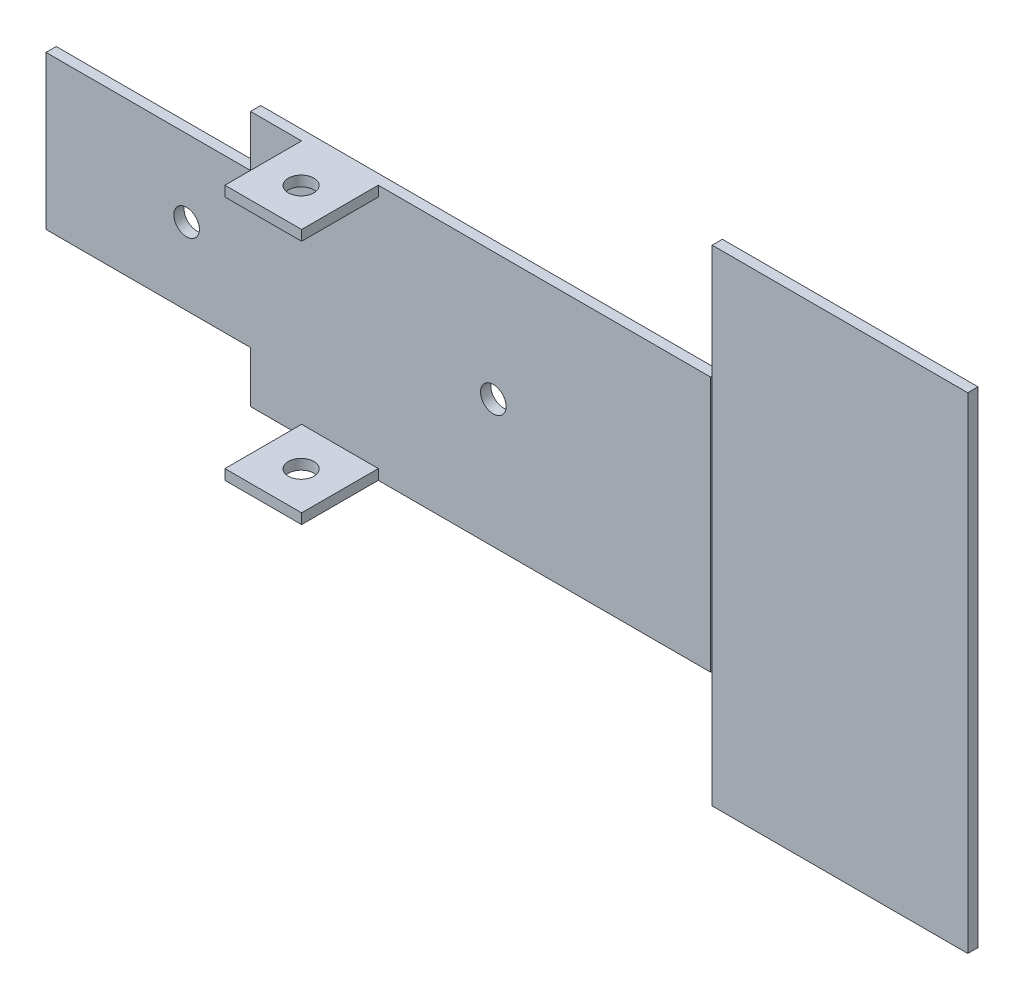
SolidWorks part; units mm, degrees
ref_plane "Front Plane" through (0, 0, 0) normal (0, 0, 1) x (1, 0, 0)
ref_plane "Top Plane" through (0, 0, 0) normal (0, 1, 0) x (1, 0, 0)
ref_plane "Right Plane" through (0, 0, 0) normal (1, 0, 0) x (0, 0, -1)
sketch "Sketch1" plane through (0, 0, 0) normal (0, 0, 1) x (1, 0, 0)
  line L1 (-65, -25) -> (65, -25)
  line L2 (-65, -25) -> (-65, 25)
  line L3 (-65, 25) -> (65, 25)
  line L4 (65, -25) -> (65, 25)
  line L5 (-65, -25) -> (65, 25) construction
  line L6 (-65, 25) -> (65, -25) construction
  line L7 (115.3074, -47.5) -> (65.3074, -47.5)
  line L8 (115.3074, -47.5) -> (115.3074, 47.5)
  line L9 (115.3074, 47.5) -> (65.3074, 47.5)
  line L10 (65.3074, -47.5) -> (65.3074, 47.5)
  line L11 (115.3074, -47.5) -> (65.3074, 47.5) construction
  line L12 (115.3074, 47.5) -> (65.3074, -47.5) construction
  line L13 (-15, 25) -> (0, 25)
  line L14 (-15, 25) -> (-15, 23)
  line L15 (-15, 23) -> (0, 23)
  line L16 (0, 25) -> (0, 23)
  line L17 (-15, -25) -> (0, -25)
  line L18 (-15, -25) -> (-15, -23)
  line L19 (-15, -23) -> (0, -23)
  line L20 (0, -25) -> (0, -23)
  point P0 (0, 0)
  point P6 (90.3074, 0)
  dimension "D1" = 130
  dimension "D2" = 50
  dimension "D3" = 95
  dimension "D4" = 50
  dimension "D5" = 2
  dimension "D6" = 15
  dimension "D7" = 50
  dimension "D8" = 2
  dimension "D9" = 15
extrude "Boss-Extrude1" add sketch "Sketch1" along normal blind 2 contours L10 L7 L8 L9 | L20 L1 L4 L3 L16 L15 L14 L2 L18 L19 region at (0.0699, 0, 0) region at (90.3074, 0, 0)
extrude "Boss-Extrude2" add sketch "Sketch1<4>" along normal blind 17 contours L16 L3 L14 L15 | L19 L20 L17 L18 region at (-7.5, 24, 0)
sketch "Sketch1<4>" plane through (0, 0, 0) normal (0, 0, 1) x (1, 0, 0) same geometry as "Sketch1"
ref_plane "Plane1" through (0, 0, 2) normal (0, 0, 1) x (1, 0, 0)
sketch "Sketch2" plane through (0, 0, 2) normal (0, 0, 1) x (1, 0, 0)
  line L0 (-7.5, -23) -> (-7.5, 23)
  line L1 (-15, -23) -> (0, -23) construction
  line L2 (-15, 23) -> (0, 23) construction
  line L3 (-7.5, 0) -> (-37.5, 0)
  line L4 (-7.5, 0) -> (22.5, 0)
  line L6 (-65, -25) -> (-25, -25)
  line L7 (-65, -25) -> (-65, -15)
  line L8 (-65, -15) -> (-25, -15)
  line L9 (-25, -25) -> (-25, -15)
  line L10 (-65, 25) -> (-25, 25)
  line L11 (-65, 25) -> (-65, 15)
  line L12 (-65, 15) -> (-25, 15)
  line L13 (-25, 25) -> (-25, 15)
  circle A0 centre (-37.5, 0) radius 2.5
  circle A1 centre (22.5, 0) radius 2.5
  dimension "D6" = 40
  dimension "D1" = 30
  dimension "D2" = 30
  dimension "D3" = 10
  dimension "D4" = 40
  dimension "D5" = 10
extrude "Cut-Extrude1" cut sketch "Sketch2" against normal blind 4 contours L13 L10 L11 L12 | L6 L9 L8 L7 | A0 | A1 region at (-45, -20, 2) region at (-45, 20, 2)
ref_plane "Plane2" through (0, -25, 0) normal (0, -1, 0) x (-1, 0, 0)
sketch "Sketch3" plane through (0, -25, 0) normal (0, -1, 0) x (-1, 0, 0)
  line L0 (7.5, -17) -> (7.5, -2.1933)
  line L1 (15, -17) -> (0, -17) construction
  circle A0 centre (7.5, -9.5967) radius 2.5
extrude "Cut-Extrude2" cut sketch "Sketch3" against normal through all contours A0
